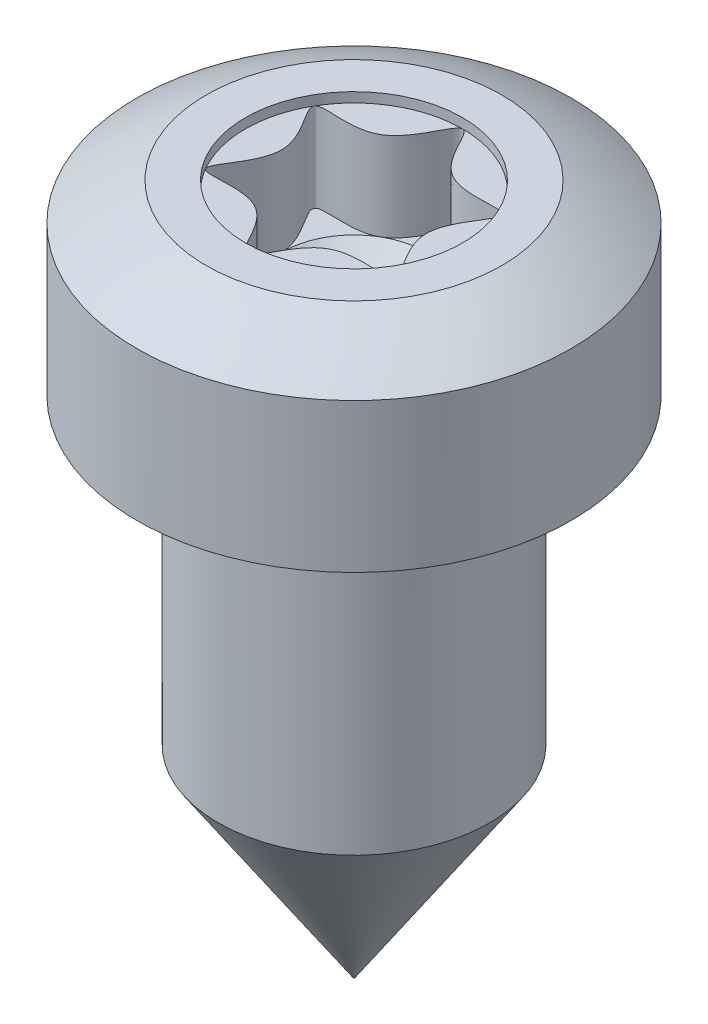
SolidWorks part; units mm, degrees
ref_plane "Front" through (0, 0, 0) normal (0, 0, 1) x (1, 0, 0)
ref_plane "Top" through (0, 0, 0) normal (0, 1, 0) x (1, 0, 0)
ref_plane "Right" through (0, 0, 0) normal (1, 0, 0) x (0, 0, -1)
sketch "Sketch1" plane through (0, 0, 0) normal (0, 0, 1) x (1, 0, 0)
  line L0 (0, 0) -> (0, 9.001) construction
  line L1 (0, 0) -> (0, 8.9)
  line L2 (0, 8.9) -> (2.8, 8.9)
  line L3 (2.8, 8.9) -> (2.8, 6.5)
  line L4 (2.8, 6.5) -> (1.75, 6.5)
  line L5 (1.75, 6.5) -> (1.75, 0)
  line L6 (1.75, 0) -> (0, 0)
  line L7 (0, 8.9) -> (-1.1, 8.9) construction
  line L8 (2.8, 6.5) -> (2.8, 5.4) construction
  line L9 (0, 0) -> (1.75, 2.6) construction
revolve "Body-Revolve" add sketch "Sketch1" angle 360 about L1
cosmetic thread "ThreadCosmetic" [suppressed] parameters "D1"=5.4, "D2"=2.3092
sketch "Sketch3" plane through (0, 0, 0) normal (0, 0, 1) x (1, 0, 0)
  line L0 (2.8, 8.42) -> (0, 4.2775) construction
  line L2 (2.8, 6.5) -> (2.8, 8.9) construction
  line L3 (0, 0) -> (0, 8.9) construction
  line L4 (2.8, 8.9) -> (-2.8, 8.9) construction
  line L5 (0, 9.2775) -> (0, 10.4044)
  line L6 (0, 10.4044) -> (5, 10.4044)
  line L7 (5, 10.4044) -> (5, 4.2775)
  arc A0 (5, 4.2775) -> (0, 9.2775) centre (0, 4.2775) ccw
  dimension "sphere_rad" = 5
  dimension "D1" = 0.48
  dimension "D2" = 1.1268
revolve "Head-Cut-Revolve" cut sketch "Sketch3" angle 360 about axis through (0, 0, 0) along (0, 1, 0)
sketch "Sketch4" plane through (0, 8.9, 0) normal (0, 1, 0) x (-1, 0, 0)
  line L0 (0, 0) -> (0, -1.54)
  line L1 (0, 0) -> (-0.7, -1.2124)
  circle A0 centre (0, 0) radius 1.4
  circle A1 centre (0, 0) radius 0.9333
  spline S0 degree 3 poles (0.302, -0.523) (0, -1.8385) (-0.302, -0.523) (-1.5922, -0.9193) (-0.6039, 0) (-1.5922, 0.9193) (-0.302, 0.523) (0, 1.8385) (0.302, 0.523) (1.5922, 0.9193) (0.6039, 0) (1.5922, -0.9193) (0.302, -0.523) (0, -1.8385) (-0.302, -0.523) knots -0.25 -0.166667 -0.083333 0 0.083333 0.166667 0.25 0.333333 0.416667 0.5 0.583333 0.666667 0.75 0.833333 0.916667 1 1.083333 1.166667 1.25 only from (0, -1.4) to (0, -1.4)
  point P4 (0, -1.4)
  point P7 (-0.4667, -0.8083)
  point P10 (-1.2124, -0.7)
  point P11 (-1.2124, 0.7)
  point P12 (0, 1.4)
  point P13 (1.2124, 0.7)
  point P14 (1.2124, -0.7)
  point P15 (-0.9333, 0)
  point P16 (-0.4667, 0.8083)
  point P17 (0.4667, 0.8083)
  point P18 (0.9333, 0)
  point P19 (0.4667, -0.8083)
  dimension "D1" = 1.8667
  dimension "D2" = 30
  dimension "D3" = 1.54
extrude "Recess-Cut-Extrude1" cut sketch "Sketch4" against normal blind 1.27 contours S0
sketch "Sketch5" plane through (0, 8.9, 0) normal (0, 1, 0) x (-1, 0, 0)
  circle A0 centre (0, 0) radius 1.4
  dimension "D1" = 2.8
extrude "Recess-Cut-Extrude2" cut sketch "Sketch5" against normal blind 0.127
sketch "Sketch6" plane through (0, 0, 0) normal (0, 0, 1) x (1, 0, 0)
  line L0 (0, 7.63) -> (0.9333, 7.63)
  line L2 (0, 0) -> (0, 8.9) construction
  line L4 (1.2177, 7.63) -> (-1.2177, 7.63) construction
  line L5 (0.9333, 7.63) -> (0, 6.74)
  line L6 (0, 6.74) -> (0, 7.63)
  line L7 (1.4, 8.9) -> (-1.4, 8.9) construction
  dimension "D1" = 2.16
  dimension "D2" = 0.9333
revolve "Drill-Cut-Revolve" cut sketch "Sketch6" angle 360 about axis through (0, 0, 0) along (0, 1, 0)
fillet "Fillet1" radius 0.1 1 edges at (0, 6.5, -1.75)
sketch "Sketch7" plane through (0, 0, 0) normal (0, 0, 1) x (1, 0, 0)
  line L0 (1.75, 0) -> (1.75, 2.6)
  line L1 (1.75, 0) -> (1.75, 6.4) construction
  line L2 (1.75, 2.6) -> (0.01, 0)
  line L3 (-1.75, 0) -> (1.75, 0) construction
  line L4 (0.01, 0) -> (1.75, 0)
  dimension "D1" = 0.01
  dimension "D2" = 2.6
revolve "Body-Cut-Revolve" cut sketch "Sketch7" angle 360 about axis through (0, 0, 0) along (0, 1, 0)
sketch "Sketch8" plane through (0, 0, 0) normal (0, 0, 1) x (1, 0, 0)
  line L0 (1.75, 5.4) -> (1.75, 4.7125)
  line L1 (1.75, 2.6) -> (1.75, 6.4) construction
  line L2 (1.75, 4.7125) -> (1.1546, 5.0563)
  line L3 (1.1546, 5.0563) -> (1.75, 5.4)
  line L4 (-2.8, 6.5) -> (2.8, 6.5) construction
  line L5 (0, 0) -> (0, 8.9) construction
  dimension "D1" = 1.1
  dimension "D2" = 1.1546
revolve "ThreadSchematic" [suppressed] cut sketch "Sketch8" angle 360 about axis through (0, 0, 0) along (0, 1, 0)
pattern_linear "ThdSchPat" [suppressed] count 5 spacing 1.1 along (0, -1, 0) of bodies 107
equation "\"D1@ThreadCosmetic\" = \"length@Sketch1\" - \"thread_gap@Sketch1\""
equation "\"D2@ThreadCosmetic\" = \"dia@Sketch1\" - \"pitch@Sketch1\" * 1.0825"
equation "\"D1@Sketch3\" = 0.2 * \"head_ht@Sketch1\""
equation "\"D1@Sketch4\" = \"socket-dia@Sketch4\" / 1.5"
equation "\"D3@Sketch4\" = \"socket-dia@Sketch4\" / 2 * 1.1"
equation "\"D1@Sketch5\" = \"socket-dia@Sketch4\""
equation "\"D1@Recess-Cut-Extrude2\" = 0.1 * \"socket-dep@Recess-Cut-Extrude1\""
equation "\"D1@Sketch6\" = 0.9 * \"head_ht@Sketch1\""
equation "\"D2@Sketch6\" = \"D1@Sketch4\" / 2"
equation "\"D2@Sketch7\" = \"end_length@Sketch1\""
equation "\"D1@Sketch8\" = \"thread_gap@Sketch1\""
equation "\"D2@Sketch8\" = \"D2@ThreadCosmetic\" / 2"
equation "\"D3@ThdSchPat\" = \"pitch@Sketch1\""
equation "\"D1@ThdSchPat\" =  ( \"length@Sketch1\" - \"thread_gap@Sketch1\" )  / \"pitch@Sketch1\""
